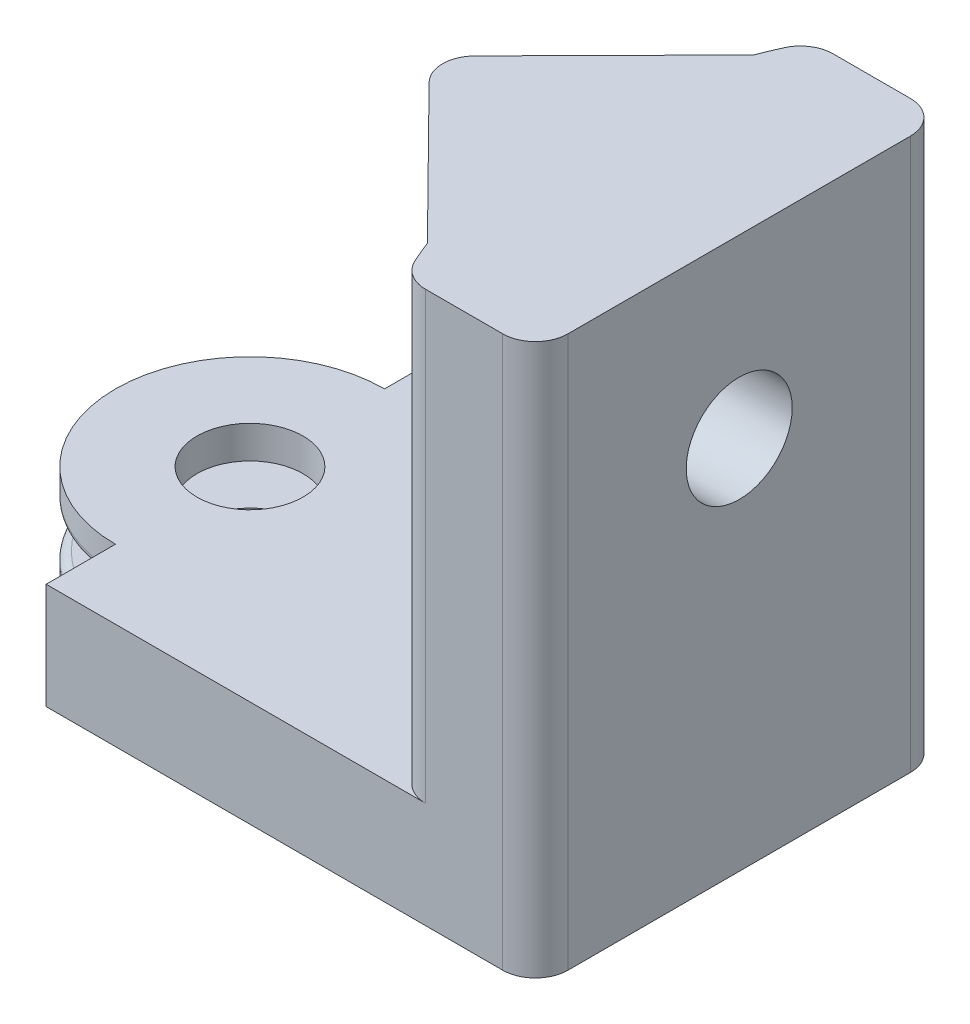
SolidWorks part; units mm, degrees
ref_plane "Front Plane" through (0, 0, 0) normal (0, 0, 1) x (1, 0, 0)
ref_plane "Top Plane" through (0, 0, 0) normal (0, 1, 0) x (1, 0, 0)
ref_plane "Right Plane" through (0, 0, 0) normal (1, 0, 0) x (0, 0, -1)
sketch "Sketch1" plane through (0, 0, 0) normal (0, 1, 0) x (1, 0, 0)
  line L0 (30, -12.5) -> (0, -12.5)
  line L1 (30, -12.5) -> (30, 12.5)
  line L2 (0, -12.5) -> (0, 12.5)
  line L3 (30, 12.5) -> (0, 12.5)
  line L4 (30, -12.5) -> (0, 12.5) construction
  line L5 (0, -12.5) -> (30, 12.5) construction
  line L6 (22, 12.5) -> (22, -12.5) construction
  circle A0 centre (0, 0) radius 3.25
  circle A1 centre (0, 0) radius 8.25
  arc A3 (0, -9.25) -> (0, 9.25) centre (0, 0) ccw
  arc A4 (22, -12.5) -> (22, 12.5) centre (46.5417, 0) cw
  point P5 (15, 0)
  point P14 (0, 0)
  point P15 (19, 0)
  dimension "D1" = 6.5
  dimension "D2" = 5
  dimension "D3" = 1
  dimension "D4" = 30
  dimension "D5" = 25
  dimension "D7" = 19
  dimension "D8" = 3
extrude "Boss-Extrude1" add sketch "Sketch1" along normal blind 2 contours L2 A1 A0 | L2 A1 A0 | L2 A3 A1 | L0 A4 L3 L2 A3 | A4 L0 L1 L3 region at (24.9493, 0, 0) region at (12.2478, 0, 0) region at (0.2068, 0, 8.75) region at (-3.8912, 0, 0) region at (3.8912, 0, 0)
extrude "Boss-Extrude2" add sketch "Sketch1<4>" along normal blind 2.5 from surface contours A3 L2 L0 L1 L3 | L3 L0 L1 region at (24.9493, 0, 0) region at (12.2478, 0, 0) starting at face at (8.625, 2, 0)
sketch "Sketch1<4>" plane through (0, 0, 0) normal (0, 1, 0) x (1, 0, 0) same geometry as "Sketch1"
extrude "Boss-Extrude3" add sketch "Sketch1<6>" along normal blind 2 from surface contours L2 A1 A0 | L2 A1 A0 | L2 A3 A1 | A3 L2 L0 L1 L3 | L3 L0 L1 region at (24.9493, 0, 0) region at (12.2478, 0, 0) region at (0.2068, 0, 8.75) region at (-3.8912, 0, 0) region at (3.8912, 0, 0) starting at face at (11.5417, 4.5, 0)
sketch "Sketch1<6>" plane through (0, 0, 0) normal (0, 1, 0) x (1, 0, 0) same geometry as "Sketch1"
extrude "Boss-Extrude6" add sketch "Sketch1<8>" along normal blind 33.8 contours A4 L0 L1 L3 region at (24.9493, 0, 0)
sketch "Sketch1<8>" plane through (0, 0, 0) normal (0, 1, 0) x (1, 0, 0) same geometry as "Sketch1"
sketch "Sketch3" plane through (0, 33.8, 0) normal (0, 1, 0) x (1, 0, 0)
  line L0 (19, 0) -> (11, 0) construction
  line L1 (11, 0) -> (20.8796, 10)
  line L2 (11, 0) -> (20.8796, -10)
  line L3 (22, -12.5) -> (30, -12.5)
  line L4 (30, -12.5) -> (30, 12.5)
  line L5 (30, 12.5) -> (22, 12.5)
  line L6 (22, -12.5) -> (30, -12.5)
  line L7 (30, -12.5) -> (30, 12.5)
  line L8 (30, 12.5) -> (22, 12.5)
  arc A0 (22, 12.5) -> (22, -12.5) centre (46.5417, 0) ccw construction
  arc A1 (22, 12.5) -> (22, -12.5) centre (46.5417, 0) ccw
  arc A2 (22, 12.5) -> (22, -12.5) centre (46.5417, 0) ccw
  arc M8 (22, 12.5) -> (22, -12.5) centre (46.5417, 0) ccw
  line M9 (22, -12.5) -> (30, -12.5)
  line M10 (30, -12.5) -> (30, 12.5)
  line M11 (30, 12.5) -> (22, 12.5)
  dimension "D2" = 8
  dimension "D3" = 20
  dimension "D1" = 0
extrude "Boss-Extrude7" add sketch "Sketch3" against normal blind 3.8 contours L0 L1 M8 | A2 L0 L2 | A2 M11 M8 M9 M10 region at (16.7152, 33.8, 3.1843) region at (16.7152, 33.8, -3.1843) region at (24.9493, 33.8, 0)
fillet "Fillet1" radius 2 1 edges at (11, 31.9, 0)
fillet "Fillet2" radius 2 4 edges at (30, 16.9, -12.5) (30, 16.9, 12.5) (22, 20.15, -12.5) (22, 20.15, 12.5)
fillet "Fillet3" radius 0.5 8 edges at (0, 3.25, -9.25) (0, 2, -8.75) (-8.25, 2, 0) (0, 2, 8.75) (0, 3.25, 9.25) (0, 4.5, 8.75) (0, 4.5, -8.75) (-8.25, 4.5, 0)
sketch "Sketch6" plane through (30, 0, 0) normal (1, 0, 0) x (0, 0, -1)
  line L0 (-10, 30) -> (10, 30) construction
  circle A0 centre (0, 23) radius 3.25
  dimension "D1" = 6.5
  dimension "D2" = 7
extrude "Cut-Extrude1" cut sketch "Sketch6" against normal up to next
